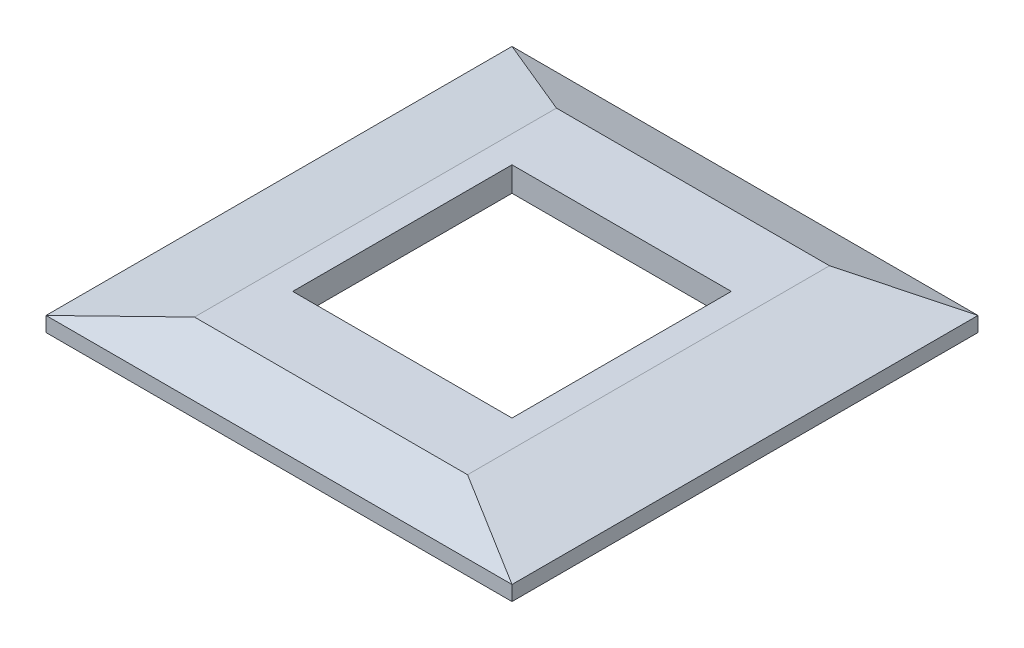
SolidWorks part; units mm, degrees
ref_plane "Спереди" through (0, 0, 0) normal (0, 0, 1) x (1, 0, 0)
ref_plane "Сверху" through (0, 0, 0) normal (0, 1, 0) x (1, 0, 0)
ref_plane "Справа" through (0, 0, 0) normal (1, 0, 0) x (0, 0, -1)
sketch "Эскиз1" plane through (0, 0, 0) normal (0, 0, 1) x (1, 0, 0)
  line L0 (0, 0) -> (-85, 0)
  line L1 (-85, 0) -> (-85, 2.7052)
  line L2 (-85, 2.7052) -> (-67.4046, 6.5)
  line L3 (-67.4046, 6.5) -> (-17.5954, 6.5)
  line L4 (0, 0) -> (0, 2.7052)
  line L5 (0, 2.7052) -> (-17.5954, 6.5)
  point P2 (0, 0)
  point P7 (-42.5, 0)
  point P8 (-42.5, 6.5)
  point P9 (0, 0)
  point P10 (0, 0)
  point P11 (0, 0)
  point P13 (0, 0)
  point P14 (0, 0)
  point P15 (0, 0)
  point P16 (0, 0)
extrude "Бобышка-Вытянуть1" add sketch "Эскиз1" along normal mid plane 85
sketch "Эскиз2" plane through (0, 0, 0) normal (1, 0, 0) x (0, 0, -1)
  line L4 (-42.5, 2.7052) -> (-42.5, 0)
  line L6 (-42.5, 0) -> (42.5, 0)
  line L9 (-42.5, 2.7052) -> (-33.0096, 6.5)
  line L10 (-42.5, 6.5) -> (42.5, 6.5) construction
  line L12 (-33.0096, 6.5) -> (33.0096, 6.5)
  line L13 (0, 21.6743) -> (0, -6.8728) construction
  line L14 (42.5, 2.7052) -> (33.0096, 6.5)
  line L15 (42.5, 2.7052) -> (42.5, 0)
  point P13 (0, 6.5)
  point P15 (0, 0)
extrude "Вырез-Вытянуть1" cut sketch "Эскиз2" against normal through all flip side to cut
sketch "Эскиз3" plane through (0, 0, 0) normal (0, -1, 0) x (1, 0, 0)
  line L1 (-62.5, 20) -> (-22.5, 20)
  line L2 (-62.5, 20) -> (-62.5, -20)
  line L3 (-62.5, -20) -> (-22.5, -20)
  line L4 (-22.5, 20) -> (-22.5, -20)
  line L5 (-62.5, 20) -> (-22.5, -20) construction
  line L6 (-62.5, -20) -> (-22.5, 20) construction
  point P0 (-42.5, 0)
  point P5 (0, 0)
extrude "Вырез-Вытянуть2" cut sketch "Эскиз3" against normal through all
sketch "Эскиз4" plane through (0, 0, 0) normal (0, -1, 0) x (1, 0, 0)
  line L17 (-83.5, 40.5) -> (-2, 40.5)
  line L18 (-83.5, 40.5) -> (-83.5, -40.5)
  line L19 (-83.5, -40.5) -> (-2, -40.5)
  line L20 (-2, 40.5) -> (-2, -40.5)
  point P4 (0, 0)
  point P5 (0, 0)
extrude "Вырез-Вытянуть3" cut sketch "Эскиз4" against normal blind 2
